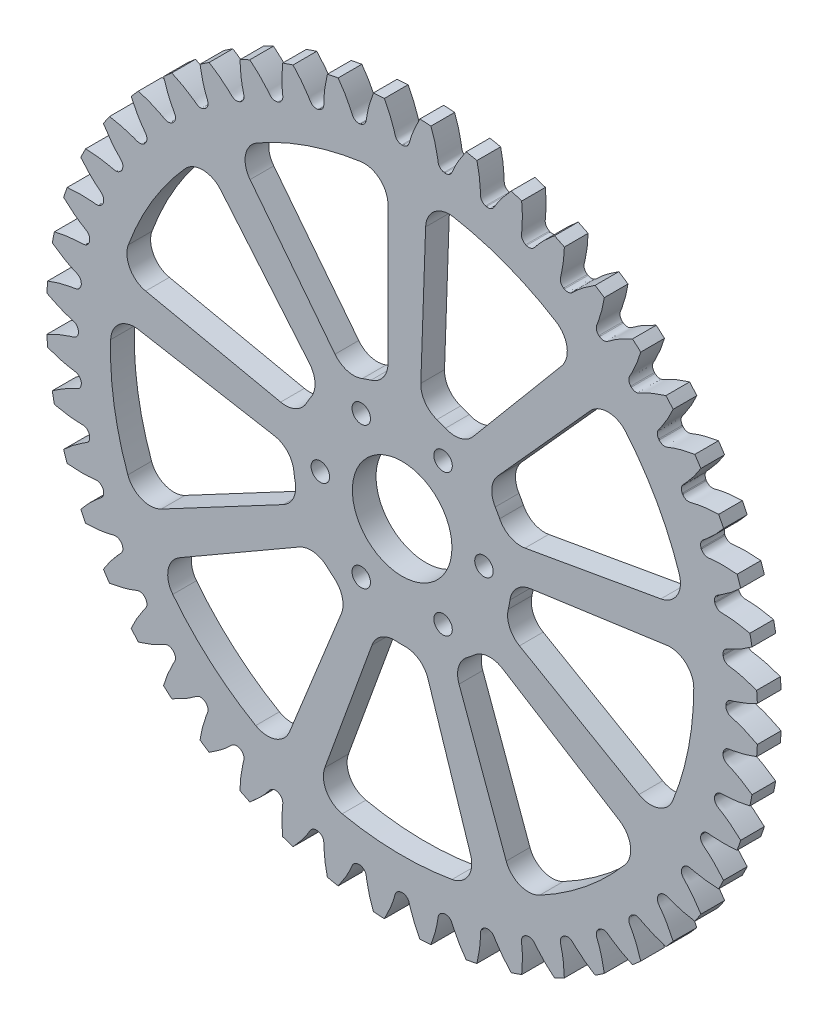
SolidWorks part; units mm, degrees
material "A-玻璃纤维"
ref_plane "前视基准面" through (0, 0, 0) normal (0, 0, 1) x (1, 0, 0)
ref_plane "上视基准面" through (0, 0, 0) normal (0, 1, 0) x (1, 0, 0)
ref_plane "右视基准面" through (0, 0, 0) normal (1, 0, 0) x (0, 0, -1)
sketch "草图1" plane through (0, 0, 0) normal (0, 0, 1) x (1, 0, 0)
  circle A0 centre (0, 0) radius 75
extrude "凸台-拉伸1" add sketch "草图1" along normal blind 5
ref_axis "基准轴1" through (0, 0, -1.5) along (0, 0, 1)
sketch "草图2" plane through (0, 0, 0) normal (0, 0, 1) x (1, 0, 0)
  line L0 (0, 0) -> (0, 75) construction
  circle A0 centre (0, 0) radius 75 construction
  arc A1 (0.0954, 68.2499) -> (-0.0954, 68.2499) centre (0, 0) ccw
  arc A2 (11.7308, 85.1642) -> (-11.7308, 85.1642) centre (0, 0) ccw
  spline S0 degree 3 poles (0.0954, 68.2499) (1.3144, 68.4075) (1.4641, 69.3226) (1.7672, 70.3184) (1.889, 70.6971) (2.0276, 71.0986) (2.1834, 71.5228) (2.3574, 71.9689) (2.5507, 72.4365) (2.7642, 72.925) (2.9987, 73.4336) (3.2551, 73.9618) (3.5344, 74.5089) (3.8373, 75.0742) (4.1647, 75.6569) (4.5174, 76.2562) (4.8962, 76.8714) (5.3019, 77.5017) (5.7352, 78.1462) (6.1969, 78.8041) (6.6876, 79.4744) (7.208, 80.1563) (7.7588, 80.8489) (8.3406, 81.5511) (8.954, 82.2621) (9.5996, 82.9808) (10.5164, 83.9612) (11.2356, 84.6849) (11.7308, 85.1642) knots 0 0 0 0 0.113354 0.131183 0.150314 0.170747 0.192481 0.215517 0.239855 0.265495 0.292437 0.32068 0.350226 0.381073 0.413222 0.446673 0.481425 0.51748 0.554836 0.593494 0.633454 0.674716 0.71728 0.761145 0.806313 0.852782 0.900553 1 1 1 1
  spline S1 degree 3 poles (-0.0954, 68.2499) (-1.3144, 68.4075) (-1.4641, 69.3226) (-1.7672, 70.3184) (-1.889, 70.6971) (-2.0276, 71.0986) (-2.1834, 71.5228) (-2.3574, 71.9689) (-2.5507, 72.4365) (-2.7642, 72.925) (-2.9987, 73.4336) (-3.2551, 73.9618) (-3.5344, 74.5089) (-3.8373, 75.0742) (-4.1647, 75.6569) (-4.5174, 76.2562) (-4.8962, 76.8714) (-5.3019, 77.5017) (-5.7352, 78.1462) (-6.1969, 78.8041) (-6.6876, 79.4744) (-7.208, 80.1563) (-7.7588, 80.8489) (-8.3406, 81.5511) (-8.954, 82.2621) (-9.5996, 82.9808) (-10.5164, 83.9612) (-11.2356, 84.6849) (-11.7308, 85.1642) knots 0 0 0 0 0.113354 0.131183 0.150314 0.170747 0.192481 0.215517 0.239855 0.265495 0.292437 0.32068 0.350226 0.381073 0.413222 0.446673 0.481425 0.51748 0.554836 0.593494 0.633454 0.674716 0.71728 0.761145 0.806313 0.852782 0.900553 1 1 1 1
extrude "切除-拉伸1" cut sketch "草图2" along normal through all
pattern_circular "阵列(圆周)1" count 48 every 7.5 about axis through (0, 0, -1.5) along (0, 0, 1) of "切除-拉伸1"
sketch "草图3" plane through (0, 0, 0) normal (0, 0, 1) x (1, 0, 0)
  circle A0 centre (0, 0) radius 72 construction
  dimension "Dn" = 144
sketch "草图4" plane through (0, 0, 5) normal (0, 0, 1) x (1, 0, 0)
  line L0 (-39.7102, 50.8267) -> (0, 0) construction
  line L1 (0, 0) -> (0, 64.5) construction
  line L2 (-34.4344, 44.074) -> (-16.5199, 21.1445) construction
  line L3 (0, 55.9308) -> (0, 26.8328) construction
  line L4 (-3, 55.9308) -> (-3, 26.8328)
  line L5 (-32.0704, 45.921) -> (-14.1559, 22.9915)
  line L6 (33.6535, 44.7738) -> (14.9497, 22.4835)
  line L7 (4.9501, 55.792) -> (3.9346, 26.7118)
  line L8 (54.5601, 12.6667) -> (25.9042, 7.6139)
  line L9 (39.6544, 39.5573) -> (20.1841, 17.9333)
  line L10 (49.9375, -25.3673) -> (24.7379, -10.8183)
  line L11 (55.804, 4.8133) -> (26.9892, 0.7636)
  line L12 (21.9485, -51.5317) -> (11.9964, -24.1885)
  line L13 (45.8422, -32.1829) -> (21.1658, -16.7634)
  line L14 (-16.3104, -53.5838) -> (-6.3583, -26.2407)
  line L15 (14.4304, -54.1204) -> (5.4386, -26.4466)
  line L16 (-46.9375, -30.5635) -> (-21.7379, -16.0145)
  line L17 (-23.7336, -50.7343) -> (-12.8333, -23.7551)
  line L18 (-55.602, 6.7579) -> (-26.9461, 1.705)
  line L19 (-50.7923, -23.6091) -> (-25.1004, -9.9484)
  line L20 (-38.2497, 40.9171) -> (-19.5459, 18.6268)
  line L21 (-54.0848, 14.5631) -> (-25.6227, 8.5133)
  circle A0 centre (0, 0) radius 17.25 construction
  circle A1 centre (-17.25, 0) radius 1.95
  circle A2 centre (-8.625, 14.9389) radius 1.95
  circle A3 centre (8.625, 14.9389) radius 1.95
  circle A4 centre (17.25, 0) radius 1.95
  circle A5 centre (8.625, -14.9389) radius 1.95
  circle A6 centre (-8.625, -14.9389) radius 1.95
  circle A7 centre (0, 0) radius 10.5
  arc A8 (-32.1134, 55.9373) -> (-9.1327, 63.8502) centre (0, 0) cw construction
  arc A9 (-7.297, 18.6213) -> (-5.7143, 19.1663) centre (0, 0) cw construction
  arc A10 (-5.7143, 19.1663) -> (0, 26.8328) centre (-8, 26.8328) ccw construction
  arc A11 (-7.297, 18.6213) -> (-16.5199, 21.1445) centre (-10.2158, 26.0698) cw construction
  arc A12 (-9.1327, 63.8502) -> (0, 55.9308) centre (-8, 55.9308) cw construction
  arc A13 (-32.1134, 55.9373) -> (-34.4344, 44.074) centre (-28.1303, 48.9993) ccw construction
  arc A14 (-6.5714, 22.0412) -> (-3, 26.8328) centre (-8, 26.8328) ccw
  arc A15 (-8.3916, 21.4145) -> (-6.5714, 22.0412) centre (0, 0) cw
  arc A16 (-8.3916, 21.4145) -> (-14.1559, 22.9915) centre (-10.2158, 26.0698) cw
  arc A17 (-30.6197, 53.3356) -> (-32.0704, 45.921) centre (-28.1303, 48.9993) ccw
  arc A18 (-30.6197, 53.3356) -> (-8.708, 60.8804) centre (0, 0) cw
  arc A19 (-8.708, 60.8804) -> (-3, 55.9308) centre (-8, 55.9308) cw
  arc A20 (9.1338, 21.1086) -> (14.9497, 22.4835) centre (11.1194, 25.6974) ccw
  arc A21 (7.3367, 21.7985) -> (9.1338, 21.1086) centre (0, 0) cw
  arc A22 (7.3367, 21.7985) -> (3.9346, 26.7118) centre (8.9316, 26.5373) cw
  arc A23 (10.8274, 60.5394) -> (4.9501, 55.792) centre (9.9471, 55.6175) ccw
  arc A24 (10.8274, 60.5394) -> (32.4625, 52.2345) centre (0, 0) cw
  arc A25 (32.4625, 52.2345) -> (33.6535, 44.7738) centre (29.8232, 47.9877) cw
  arc A26 (20.5653, 10.299) -> (25.9042, 7.6139) centre (25.036, 12.5379) ccw
  arc A27 (19.632, 11.9827) -> (20.5653, 10.299) centre (0, 0) cw
  arc A28 (19.632, 11.9827) -> (20.1841, 17.9333) centre (23.8998, 14.5876) cw
  arc A29 (47.2082, 39.4162) -> (39.6544, 39.5573) centre (43.3701, 36.2116) ccw
  arc A30 (47.2082, 39.4162) -> (58.4434, 19.1474) centre (0, 0) cw
  arc A31 (58.4434, 19.1474) -> (54.5601, 12.6667) centre (53.6919, 17.5907) cw
  arc A32 (22.374, -5.3296) -> (24.7379, -10.8183) centre (27.2379, -6.4882) ccw
  arc A33 (22.7413, -3.4399) -> (22.374, -5.3296) centre (0, 0) cw
  arc A34 (22.7413, -3.4399) -> (26.9892, 0.7636) centre (27.6851, -4.1877) cw
  arc A35 (61.4998, -0.1503) -> (55.804, 4.8133) centre (56.4998, -0.1381) ccw
  arc A36 (61.4998, -0.1503) -> (57.0779, -22.8989) centre (0, 0) cw
  arc A37 (57.0779, -22.8989) -> (49.9375, -25.3673) centre (52.4375, -21.0372) cw
  arc A38 (13.7137, -18.4644) -> (11.9964, -24.1885) centre (16.6949, -22.4784) ccw
  arc A39 (15.2097, -17.253) -> (13.7137, -18.4644) centre (0, 0) cw
  arc A40 (15.2097, -17.253) -> (21.1658, -16.7634) centre (18.5162, -21.0036) cw
  arc A41 (47.015, -39.6465) -> (45.8422, -32.1829) centre (43.1926, -36.4232) ccw
  arc A42 (47.015, -39.6465) -> (29.0051, -54.2305) centre (0, 0) cw
  arc A43 (29.0051, -54.2305) -> (21.9485, -51.5317) centre (26.647, -49.8216) cw
  arc A44 (-1.3634, -22.9596) -> (-6.3583, -26.2407) centre (-1.6598, -27.9508) ccw
  arc A45 (0.5613, -22.9931) -> (-1.3634, -22.9596) centre (0, 0) cw
  arc A46 (0.5613, -22.9931) -> (5.4386, -26.4466) centre (0.6833, -27.9917) cw
  arc A47 (10.5313, -60.5916) -> (14.4304, -54.1204) centre (9.6751, -55.6655) ccw
  arc A48 (10.5313, -60.5916) -> (-12.6395, -60.1871) centre (0, 0) cw
  arc A49 (-12.6395, -60.1871) -> (-16.3104, -53.5838) centre (-11.6119, -55.2939) cw
  arc A50 (-15.8026, -16.7116) -> (-21.7379, -16.0145) centre (-19.2379, -20.3446) ccw
  arc A51 (-14.3497, -17.9746) -> (-15.8026, -16.7116) centre (0, 0) cw
  arc A52 (-14.3497, -17.9746) -> (-12.8333, -23.7551) centre (-17.4692, -21.8821) cw
  arc A53 (-30.8801, -53.1852) -> (-23.7336, -50.7343) centre (-28.3695, -48.8612) ccw
  arc A54 (-30.8801, -53.1852) -> (-48.37, -37.9815) centre (0, 0) cw
  arc A55 (-48.37, -37.9815) -> (-46.9375, -30.5635) centre (-44.4375, -34.8936) cw
  arc A56 (-22.8475, -2.6442) -> (-26.9461, 1.705) centre (-27.8144, -3.219) ccw
  arc A57 (-22.5464, -4.5455) -> (-22.8475, -2.6442) centre (0, 0) cw
  arc A58 (-22.5464, -4.5455) -> (-25.1004, -9.9484) centre (-27.4477, -5.5337) cw
  arc A59 (-57.8423, -20.8929) -> (-50.7923, -23.6091) centre (-53.1397, -19.1943) ccw
  arc A60 (-57.8423, -20.8929) -> (-61.4676, 1.9961) centre (0, 0) cw
  arc A61 (-61.4676, 1.9961) -> (-55.602, 6.7579) centre (-56.4702, 1.8338) cw
  arc A62 (-19.2018, 12.6605) -> (-19.5459, 18.6268) centre (-23.3762, 15.4128) ccw
  arc A63 (-20.1933, 11.0105) -> (-19.2018, 12.6605) centre (0, 0) cw
  arc A64 (-20.1933, 11.0105) -> (-25.6227, 8.5133) centre (-24.5832, 13.404) cw
  arc A65 (-57.7395, 21.1754) -> (-54.0848, 14.5631) centre (-53.0452, 19.4538) ccw
  arc A66 (-57.7395, 21.1754) -> (-45.8038, 41.0397) centre (0, 0) cw
  arc A67 (-45.8038, 41.0397) -> (-38.2497, 40.9171) centre (-42.08, 37.7031) cw
  point P22 (0, 20)
  point P25 (-12.3132, 15.7602)
  point P144 (0, 0)
  dimension "D1" = 34.5
  dimension "D2" = 3.9
  dimension "D4" = 21
  dimension "D5" = 64.5
  dimension "D6" = 20
  dimension "D8" = 8
  dimension "D9" = 8
  dimension "D7" = 38
  dimension "D10" = 3
  dimension "D3" = 6
  dimension "D11" = 9
extrude "切除-拉伸3" cut sketch "草图4" against normal blind 10
